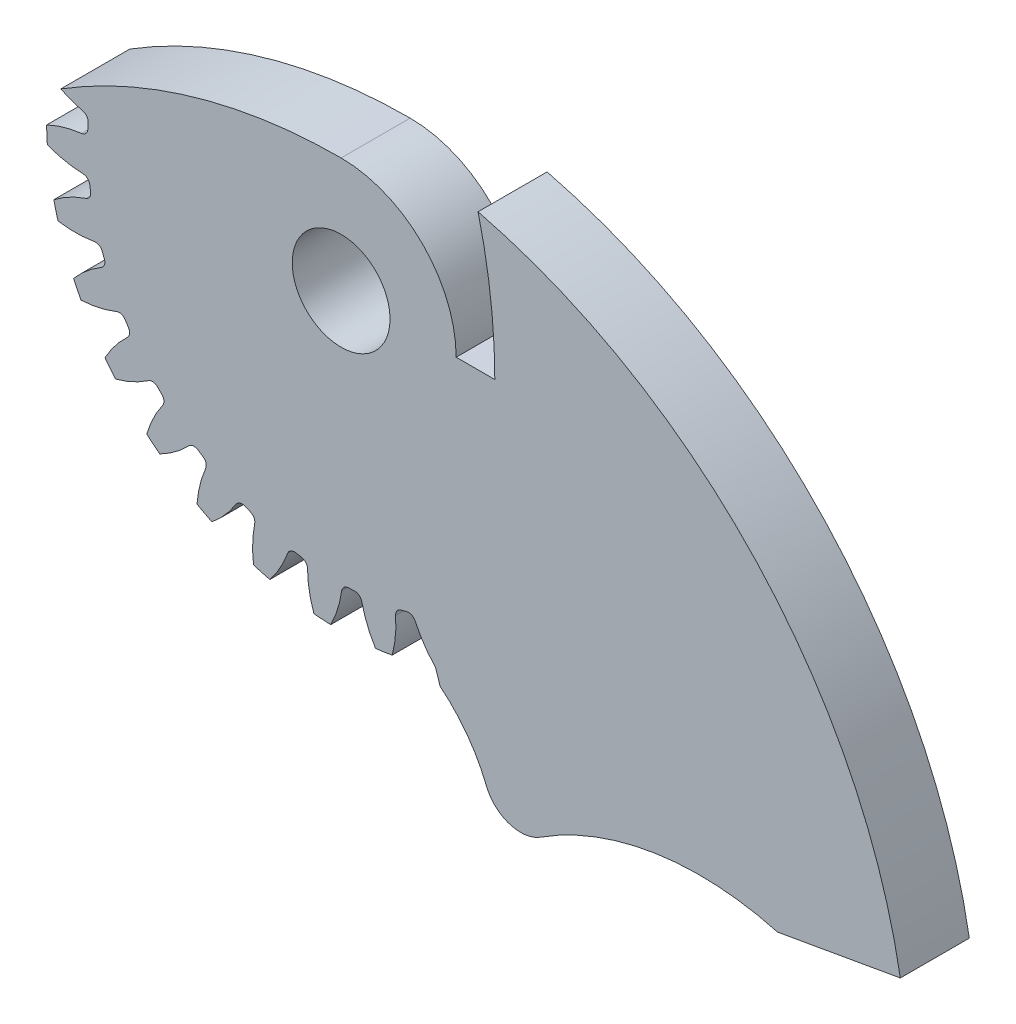
SolidWorks part; units mm, degrees
material "ABS"
ref_plane "Front" through (0, 0, 0) normal (0, 0, 1) x (1, 0, 0)
ref_plane "Top" through (0, 0, 0) normal (0, 1, 0) x (1, 0, 0)
ref_plane "Right" through (0, 0, 0) normal (1, 0, 0) x (0, 0, -1)
sketch "Sketch3" plane through (0, 0, 0) normal (0, 0, 1) x (1, 0, 0)
  circle A0 centre (0, 0) radius 40.64
  dimension "od" = 81.28
extrude "gearBody" add sketch "Sketch3" along normal blind 9.525
sketch "Sketch2" plane through (0, 0, 0) normal (0, 0, 1) x (1, 0, 0)
  line L0 (0, 0) -> (34.0786, 14.1158) construction
  line L1 (45.4751, -11.4855) -> (0, 0) construction
  line L2 (0, 0) -> (36.3143, 0) construction
  line L3 (38.0972, -0.458) -> (37.8451, -4.4001) construction
  line L5 (37.9712, -2.4291) -> (0, 0) construction
  line L7 (0, 0) -> (36.8864, 0) construction
  arc A0 (36.879, -0.7403) -> (36.6727, -3.9649) centre (0, 0) ccw construction
  arc A1 (40.637, 0.4947) -> (40.2427, -5.6687) centre (0, 0) ccw construction
  arc A2 (38.0972, -0.458) -> (37.8451, -4.4001) centre (0, 0) ccw construction
  arc A3 (34.9015, -2.6404) -> (34.9534, -1.8283) centre (0, 0) ccw
  arc A4 (45.4751, -11.4855) -> (35.6466, -3.6712) centre (32.0022, -18.3431) ccw
  arc A5 (45.4751, -11.4855) -> (46.5679, 5.5974) centre (0, 0) ccw
  arc A6 (46.5679, 5.5974) -> (35.8238, -0.9008) centre (34.0786, 14.1158) cw
  arc A7 (34.9534, -1.8283) -> (35.8238, -0.9008) centre (35.9376, -1.8798) cw
  arc A8 (35.6466, -3.6712) -> (34.9015, -2.6404) centre (35.8842, -2.7147) cw
  point P6 (46.5679, 5.5974)
  point P22 (45.4751, -11.4855)
  dimension "baseDia" = 73.7729
  dimension "od" = 81.28
  dimension "pd" = 76.2
  dimension "rd" = 70.0024
  dimension "rFillet" = 0.9855
  dimension "pointX" = 46.5679
  dimension "pointY" = 5.5974
  dimension "CTT" = 3.9421
  dimension "flankCenterAngle" = 22.5
extrude "toothCut" cut sketch "Sketch2" along normal through all
pattern_circular "CirPattern1" count 30 over 360 about axis through (0, 0, 9.525) along (0, 0, -1) of "toothCut"
sketch "hub1Dia" plane through (0, 0, 0) normal (0, 0, -1) x (-1, 0, 0)
  circle A0 centre (0, 0) radius 12.7
  dimension "hub1Dia" = 25.4
sketch "hub2Dia" plane through (0, 0, 9.525) normal (0, 0, 1) x (1, 0, 0)
  circle A0 centre (0, 0) radius 12.7
  dimension "hub2dia" = 25.4
sketch "boreDia" plane through (0, 0, 0) normal (0, 0, 1) x (1, 0, 0)
  circle A0 centre (0, 0) radius 6.7469
  dimension "boreDia" = 13.4937
extrude "bore" cut sketch "boreDia" against normal mid plane 25400
sketch "Sketch4" plane through (0, 0, 9.525) normal (0, 0, 1) x (1, 0, 0)
  circle A0 centre (0, -57.15) radius 78.359
  arc A2 (-42.9159, 8.4119) -> (42.9159, 8.4119) centre (0, 0) cw
  dimension "D1" = 156.718
  dimension "D2" = 57.15
extrude "Cut-Extrude1" cut sketch "Sketch4" against normal through all contours A0 region at (0, 27.8712, 9.525)
sketch "Sketch5" plane through (0, 0, 9.525) normal (0, 0, 1) x (1, 0, 0)
  line L0 (0, 21.209) -> (21.5163, 7.6712)
  line L1 (21.5163, 7.6712) -> (8.9608, -26.928)
  line L2 (8.9608, -26.928) -> (13.028, -38.4952)
  line L3 (0, 0) -> (0, -57.15) construction
  line L4 (0, -57.15) -> (-49.4328, 3.6491) construction
  line L5 (0, -57.15) -> (67.8609, -96.3295) construction
  line L6 (13.6543, -40.4261) -> (13.028, -38.4952)
  line L9 (0, -57.15) -> (77.1686, -43.5431) construction
  line L12 (60.232, -46.5295) -> (77.1686, -43.5431)
  circle A1 centre (0, -57.15) radius 78.359 construction
  arc A5 (0, 21.209) -> (77.1686, -43.5431) centre (0, -57.15) cw
  circle A6 centre (0, -57.15) radius 21.59 construction
  arc A10 (20.0525, -49.1485) -> (13.6543, -40.4261) centre (0, -57.15) ccw
  circle A12 centre (49.4934, -85.725) radius 40.64 construction
  arc A13 (27.5177, -51.539) -> (60.232, -46.5295) centre (49.4934, -85.725) cw
  arc A14 (27.5177, -51.539) -> (20.0525, -49.1485) centre (24.7708, -47.2658) cw
  point P28 (21.569, -56.1981)
  dimension "D1" = 43.18
  dimension "D3" = 81.28
  dimension "D7" = 5.08
  dimension "D6" = 156.718
  dimension "D2" = 120
  dimension "D4" = 57.15
  dimension "D5" = 80
extrude "Boss-Extrude1" add sketch "Sketch5" against normal up to surface (9.525 mm away) up to face at (6.7469, 0, 0)
sketch "Sketch6" plane through (0, 0, 9.525) normal (0, 0, 1) x (1, 0, 0)
  line L1 (-41.2829, 3.086) -> (-43.5386, 8)
  line L2 (15.875, 0) -> (21.209, 0)
  circle A0 centre (0, -57.15) radius 78.359 construction
  arc A1 (77.1686, -43.5431) -> (-36.286, 12.3011) centre (0, -57.15) ccw construction
  circle A2 centre (0, 0) radius 15.875 construction
  arc A3 (0, 15.875) -> (15.875, 0) centre (0, 0) cw
  arc A4 (18.8964, 18.8964) -> (-43.5386, 8) centre (0, -57.15) ccw
  arc A5 (0, 15.875) -> (-41.2829, 3.086) centre (0, -57.15) ccw
  circle A6 centre (0, 0) radius 21.209 construction
  circle A8 centre (-57.15, 0) radius 78.359 construction
  arc A9 (21.209, 0) -> (18.8964, 18.8964) centre (-57.15, 0) ccw
  dimension "D4" = 57.15
  dimension "D1" = 31.75
  dimension "D2" = 42.418
  dimension "D3" = 156.718
extrude "Cut-Extrude2" cut sketch "Sketch6" against normal through all
equation "\"Bodytube_OD\" = 6.17in"
equation "\"Bodytube_ID\" = 5.998in"
equation "\"Fwd_Tube_Length\" = 38in"
equation "\"Mid_Tube_Length\" = 8in"
equation "\"Aft_Section_Length\"= 40in"
equation "\"Mid_Coupler_Length\"= 13in"
equation "\"Aft_Lower_Length\"= 22in"
equation "\"AB_Coupler_OD_Length\"= 1in"
equation "\"AB_Coupling_Section_Length\"= 0.375in"
equation "\"AB_Coupler_Length\"= \"AB_Coupler_OD_Length\" + \"AB_Coupling_Section_Length\" * 2"
equation "\"Cutout_Angle\" = 80"
equation "\"AB_Paddle_Height\" = 0.375in"
equation "\"AB_Coupler_Num_Screws\"= 6"
equation "\"Num_Cutouts\" = 3"
equation "\"AB_Coupler_OD\"= 6.17in"
equation "\"AB_Coupler_ID\"= 5.75in"
equation "\"AB_Coupler_Surface_Diameter\"= 5.998in"
equation "\"AB_Coupling_Screw_Diameter\"= 0.1065in"
equation "\"AB_Central_Bushing_Length\" = .75in"
equation "\"Lead_Screw_Dist\" = 2.25in"
equation "\"Lead_Screw_Diam\" = (27/64)*1in"
equation "\"Lead_Screw_Length\" = (\"Mid_Coupler_Length\" + 2*0.375in + 2*0.5in)"
equation "\"Paddle_Pin_Offset\" = .25in"
equation "\"Paddle_Pin_Radius\" = 2.25in"
equation "\"Fwd_BKHD_From_Top\" = 18in"
equation "\"D1@Sketch4\"=\"Bodytube_OD\""
equation "\"D2@Sketch4\"=\"Paddle_Pin_Radius\""
equation "\"D3@Sketch5\"=\"Paddle_Gear_OD\""
equation "\"D4@Sketch5\"=\"Paddle_Pin_Radius\""
equation "\"Motor_OD\" = 4in"
equation "\"Aft_Upper_Length\"= \"Aft_Section_Length\" - \"Aft_Lower_Length\" - \"AB_Coupler_OD_Length\""
equation "\"Paddle_Gear_OD\" = 3.2in"
equation "\"D5@Sketch5\"=\"Cutout_Angle\""
equation "\"D6@Sketch5\"=\"Bodytube_OD\""
equation "\"D1@Sketch6\"=\"AB_Coupler_ID\"-2*\"Paddle_Pin_Radius\""
equation "\"D2@Sketch6\"=\"Bodytube_OD\"-2*\"Paddle_Pin_Radius\""
equation "\"D3@Sketch6\"=\"Bodytube_OD\""
equation "\"D4@Sketch6\"=\"Paddle_Pin_Radius\""
